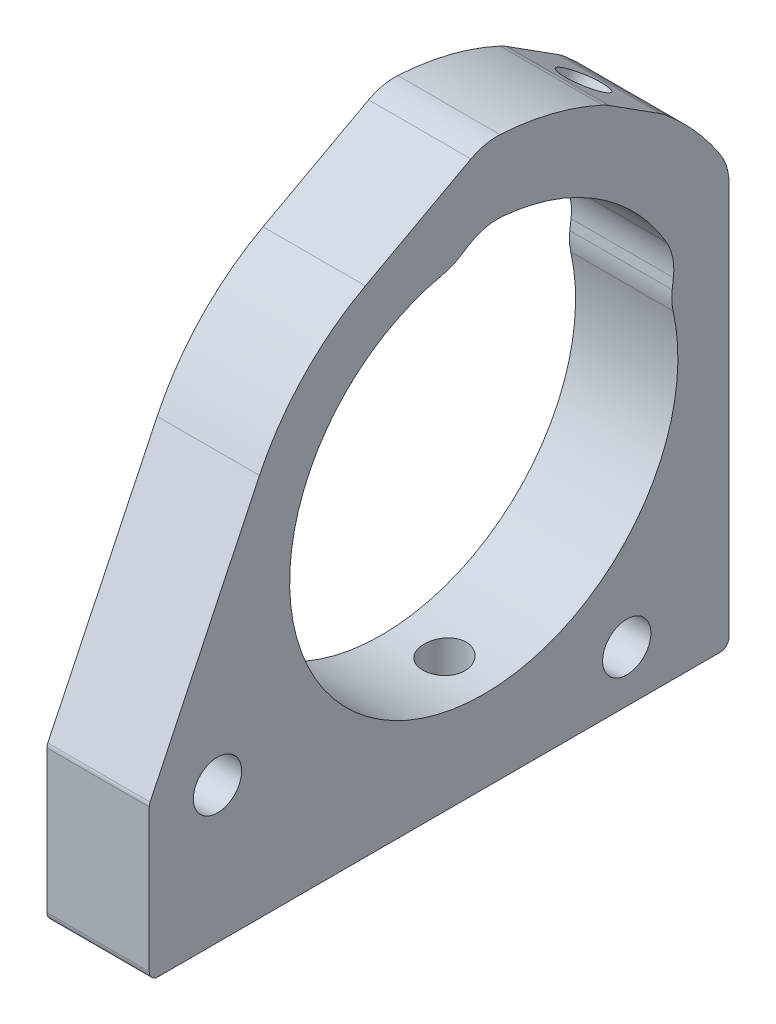
SolidWorks part; units mm, degrees
material "Alum Plate"
ref_plane "Front Plane" through (0, 0, 0) normal (0, 0, 1) x (1, 0, 0)
ref_plane "Top Plane" through (0, 0, 0) normal (0, 1, 0) x (1, 0, 0)
ref_plane "Right Plane" through (0, 0, 0) normal (1, 0, 0) x (0, 0, -1)
other "Bounding Box"
ref_plane "Default Plane" through (0, 2.286, 19.05) normal (0, -1, 0) x (-1, 0, 0)
sketch "Sketch1" plane through (0, 0, 0) normal (1, 0, 0) x (0, 0, -1)
  line L0 (-31.1404, -25.6921) -> (22.8346, -25.6921)
  line L2 (-31.1404, -25.6921) -> (-31.1404, -11.4046)
  line L3 (-31.1404, -11.4046) -> (-20.8778, 10.0068)
  line L4 (22.8346, -25.6921) -> (22.8346, 3.8211)
  line L6 (0, 19.6596) -> (0, 18.0721)
  line L7 (16.3789, 7.6376) -> (17.8176, 8.3085)
  line L8 (0, 26.3271) -> (-11.0223, 20.36)
  line L9 (22.8346, 3.8211) -> (22.8346, 13.1033)
  line L10 (11.3645, 23.7479) -> (16.7201, 20.3361)
  line L11 (0, 0) -> (14.0423, 22.042) construction
  arc A0 (0, 18.0721) -> (16.3789, 7.6376) centre (0, 0) ccw
  arc A1 (-11.0223, 20.36) -> (-20.8778, 10.0068) centre (0, 0) ccw
  circle A2 centre (0, 0) radius 23.1521 construction
  circle A3 centre (13.3096, -20.9169) radius 2.2479
  circle A4 centre (-24.7904, -12.9921) radius 2.2479
  arc A5 (17.8176, 8.3085) -> (0, 19.6596) centre (0, 0) ccw
  arc A6 (16.3789, 7.6376) -> (0, 18.0721) centre (0, 0) ccw construction
  circle A7 centre (0, 0) radius 18.0721 construction
  arc A8 (22.8346, 13.1033) -> (16.7201, 20.3361) centre (0, 0) ccw
  arc A9 (22.8346, 3.8211) -> (-11.0223, 20.36) centre (0, 0) ccw construction
  arc A10 (11.3645, 23.7479) -> (0, 26.3271) centre (0, 0) ccw
  point P23 (10.5631, 16.5807)
  dimension "D1" = 36.1442
  dimension "D8" = 4.4958
  dimension "D11" = 5.08
  dimension "D12" = 1.5875
  dimension "D14" = 3.175
  dimension "D2" = 25.6921
  dimension "D3" = 22.8346
  dimension "D4" = 6.35
  dimension "D5" = 14.2875
  dimension "D6" = 4.7752
  dimension "D7" = 9.525
  dimension "D9" = 12.7
  dimension "D10" = 47.625
  dimension "D13" = 65
  dimension "D15" = 6.35
  dimension "D16" = 6.4753
extrude "Boss-Extrude1" add sketch "Sketch1" along normal mid plane 9.525
sketch "Sketch2" plane through (0, -25.6921, 0) normal (0, -1, 0) x (1, 0, 0)
  line L1 (0, 31.1404) -> (0, 24.3053) construction
  line L2 (4.7625, 31.1404) -> (-4.7625, 31.1404) construction
  line L3 (0, 24.3053) -> (0, -1.0947) construction
  line L4 (4.7625, -22.8346) -> (-4.7625, -22.8346) construction
  circle A0 centre (0, -1.0947) radius 2.0193
  circle A1 centre (0, 24.3053) radius 2.0193
  dimension "D2" = 4.0386
  dimension "D1" = 21.7399
  dimension "D3" = 25.4
extrude "Cut-Extrude1" cut sketch "Sketch2" against normal blind 9.525
fillet "Fillet1" radius 0.8255 3 edges at (0, -25.6921, 31.1404) (0, -11.4046, 31.1404) (0, -25.6921, -22.8346)
chamfer "Chamfer1" distance 3.302 angle 30 2 edges at (0, 7.6376, -16.3789) (0, 18.0721, 0) first distance on face at (0.4462, -18.0509, 0.8746)
fillet "Fillet2" radius 5.08 4 edges at (0, 13.1033, -22.8346) (0, 20.3361, -16.7201) (0, 23.7479, -11.3645) (0, 26.3271, 0)
fillet "Fillet3" radius 5.08 4 edges at (0, 8.2447, -17.8473) (0, 4.8255, -17.416) (0, 19.6595, 0.0703) (0, 17.8236, 2.9869)
sketch "Sketch4" plane through (0, 22.042, -14.0423) normal (0, 0.8434, -0.5373) x (1, 0, 0)
  circle A0 centre (0, 0) radius 2.0193
  dimension "D1" = 4.0386
extrude "Cut-Extrude2" cut sketch "Sketch4" against normal up to next
equation "\"Unit Measure\"= \"BoundingVolume\" / \"Thickness\"'in^2"
